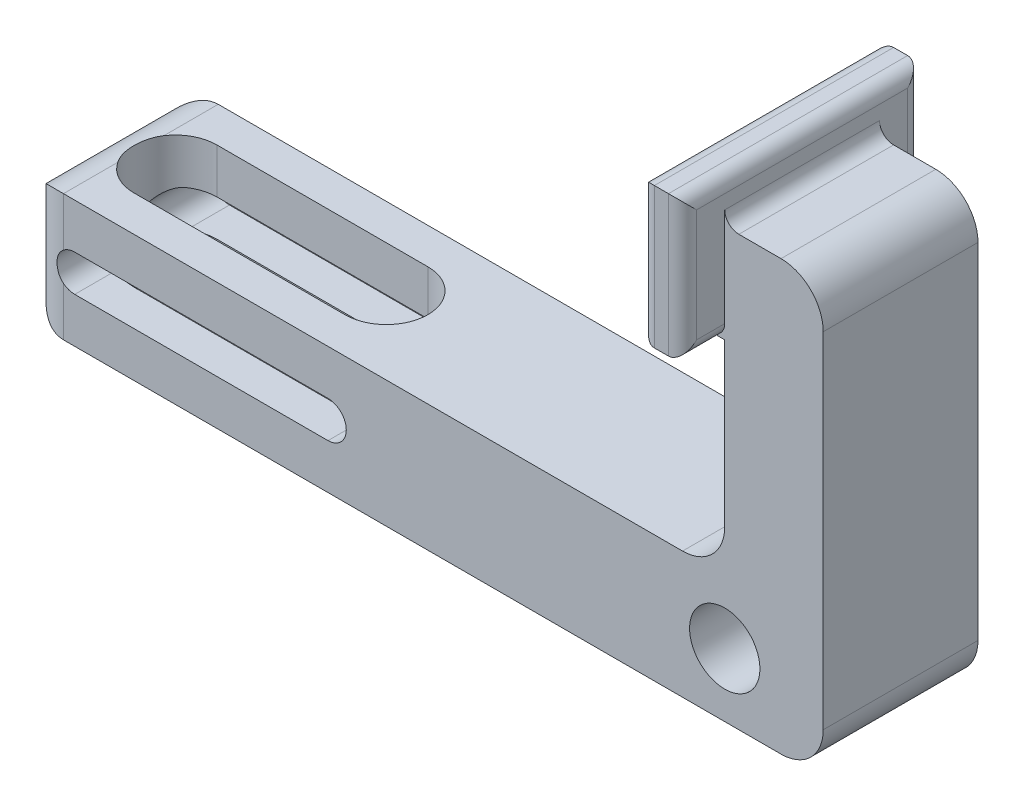
SolidWorks part; units mm, degrees
ref_plane "Front Plane" through (0, 0, 0) normal (0, 0, 1) x (1, 0, 0)
ref_plane "Top Plane" through (0, 0, 0) normal (0, 1, 0) x (1, 0, 0)
ref_plane "Right Plane" through (0, 0, 0) normal (1, 0, 0) x (0, 0, -1)
sketch "Sketch1" plane through (0, 0, 0) normal (0, 0, 1) x (1, 0, 0)
  line L0 (0, 0) -> (57, 0)
  line L1 (57, 0) -> (57, 30.5)
  line L2 (57, 30.5) -> (50, 30.5)
  line L3 (50, 30.5) -> (50, 9)
  line L4 (50, 9) -> (0, 9)
  line L5 (0, 9) -> (0, 0)
  dimension "D1" = 9
  dimension "D2" = 7
  dimension "D3" = 21.5
  dimension "D4" = 50
extrude "Boss-Extrude1" add sketch "Sketch1" against normal blind 11
sketch "Sketch2" plane through (0, 0, 0) normal (0, -1, 0) x (1, 0, 0)
  line L0 (0, -5.5) -> (57, -5.5) construction
  line L1 (0, -11) -> (0, 0) construction
  line L2 (57, -11) -> (57, 0) construction
  line L3 (5.45, -5.5) -> (20.45, -5.5) construction
  line L4 (5.45, -2.55) -> (20.45, -2.55)
  line L5 (5.45, -8.45) -> (20.45, -8.45)
  arc A0 (5.45, -2.55) -> (5.45, -8.45) centre (5.45, -5.5) ccw
  arc A1 (20.45, -8.45) -> (20.45, -2.55) centre (20.45, -5.5) ccw
  point P8 (12.95, -5.5)
  point P13 (2.5, -5.5)
  dimension "D1" = 5.9
  dimension "D2" = 2.5
  dimension "D3" = 15
extrude "Cut-Extrude1" cut sketch "Sketch2" against normal through all contours L5 A1 L4 A0
sketch "Sketch3" plane through (0, 0, 0) normal (0, 0, 1) x (1, 0, 0)
  line L0 (0, 4.5) -> (57, 4.5) construction
  line L1 (0, 9) -> (0, 0) construction
  line L2 (57, 0) -> (57, 30.5) construction
  line L3 (3.8, 4.5) -> (21.8, 4.5) construction
  line L4 (3.8, 5.8) -> (21.8, 5.8)
  line L5 (3.8, 3.2) -> (21.8, 3.2)
  arc A0 (3.8, 5.8) -> (3.8, 3.2) centre (3.8, 4.5) ccw
  arc A1 (21.8, 3.2) -> (21.8, 5.8) centre (21.8, 4.5) ccw
  point P8 (12.8, 4.5)
  point P13 (2.5, 4.5)
  dimension "D1" = 2.6
  dimension "D2" = 2.5
  dimension "D3" = 18
extrude "Cut-Extrude2" cut sketch "Sketch3" against normal through all
sketch "Sketch4" plane through (50, 0, 0) normal (-1, 0, 0) x (0, 0, 1)
  line L0 (-11, 30.5) -> (0, 30.5) construction
  line L1 (-14, 33.5) -> (3, 33.5)
  line L2 (-14, 33.5) -> (-14, 23.5)
  line L3 (-14, 23.5) -> (3, 23.5)
  line L4 (3, 33.5) -> (3, 23.5)
  line L5 (-11, 30.5) -> (-11, 9) construction
  line L6 (0, 30.5) -> (0, 9) construction
  dimension "D1" = 7
  dimension "D2" = 3
  dimension "D3" = 3
  dimension "D4" = 3
extrude "Boss-Extrude2" add sketch "Sketch4" along normal blind 3
sketch "Sketch5" plane through (0, 0, 0) normal (0, 0, 1) x (1, 0, 0)
  line L0 (50, 9) -> (50, 0) construction
  line L1 (0, 0) -> (57, 0) construction
  circle A0 centre (50, 4.5) radius 2.5
  dimension "D1" = 5
extrude "Cut-Extrude3" cut sketch "Sketch5" against normal through all
fillet "Fillet1" radius 3 2 edges at (50, 9, -5.5) (57, 0, -5.5)
fillet "Fillet2" radius 3 4 edges at (0, 0, -5.5) (0, 9, -5.5) (0, 4.5, -11) (0, 4.5, 0)
fillet "Fillet3" radius 1 8 edges at (50, 23.5, 1.5) (50, 28.5, -14) (50, 33.5, -5.5) (50, 28.5, 3) (47, 28.5, -14) (47, 28.5, 3) (47, 23.5, -5.5) (47, 33.5, -5.5)
fillet "Fillet4" radius 3 1 edges at (57, 30.5, -5.5)
fillet "Fillet5" radius 1 1 edges at (50, 30.5, -5.5)
